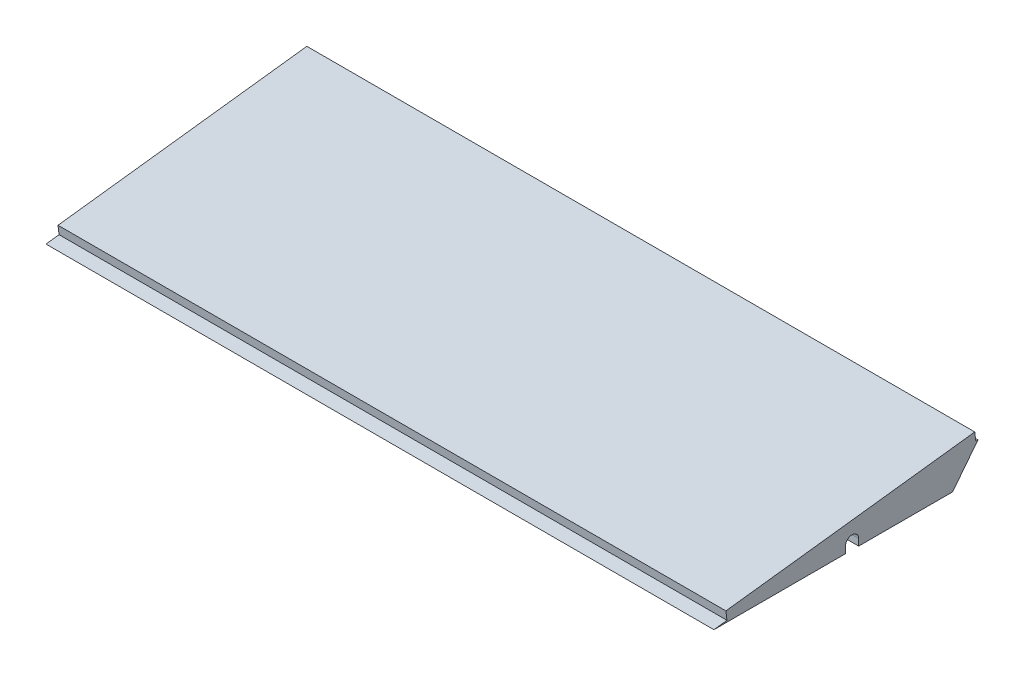
SolidWorks part; units mm, degrees
ref_plane "Front Plane" through (0, 0, 0) normal (0, 0, 1) x (1, 0, 0)
ref_plane "Top Plane" through (0, 0, 0) normal (0, 1, 0) x (1, 0, 0)
ref_plane "Right Plane" through (0, 0, 0) normal (1, 0, 0) x (0, 0, -1)
sketch "Sketch1" plane through (0, 0, 0) normal (1, 0, 0) x (0, 0, -1)
  line L0 (0, 0) -> (34.5629, 4.2438)
  line L2 (0, 0) -> (29.8632, 0)
  dimension "D1" = 7
ref_plane "Plane1" through (0, 0, 0) normal (0, -0.9925, -0.1219) x (0, 0.1219, -0.9925)
sketch "Sketch2" plane through (0, 0, 0) normal (0, -0.9925, -0.1219) x (0, 0.1219, -0.9925)
  line L1 (0, 0) -> (121.3, 0)
  line L2 (0, 0) -> (0, 304.5)
  line L3 (0, 304.5) -> (121.3, 304.5)
  line L4 (121.3, 0) -> (121.3, 304.5)
  dimension "D1" = 304.5
  dimension "D2" = 121.3
extrude "Boss-Extrude1" add sketch "Sketch2" along normal blind 20
sketch "Sketch4" plane through (304.5, 0, 0) normal (1, 0, 0) x (0, 0, -1)
  line L0 (0, 0) -> (5.9553, 0.7312)
  line L1 (-4.5988, -0.5647) -> (4.5988, 0.5647) construction
  line L2 (5.9553, 0.7312) -> (6.4428, -3.239)
  line L3 (6.4428, -3.239) -> (0.4875, -3.9702)
  line L4 (2.4374, -19.8509) -> (0, 0) construction
  line L5 (0.4875, -3.9702) -> (0, 0)
  line L6 (119.4033, 14.6609) -> (119.8908, 10.6907)
  line L7 (120.3958, 14.7828) -> (0, 0) construction
  line L8 (119.8908, 10.6907) -> (120.8833, 10.8126)
  line L9 (122.8332, -5.0682) -> (120.3958, 14.7828) construction
  line L10 (120.8833, 10.8126) -> (120.3958, 14.7828)
  line L11 (120.3958, 14.7828) -> (119.4033, 14.6609)
  line L12 (0.4875, -3.9702) -> (109.3338, -3.9702)
  line L13 (109.3338, -3.9702) -> (120.8833, 10.8126)
  line L14 (0.4875, -3.9702) -> (2.4374, -19.8509)
  line L15 (2.4374, -19.8509) -> (122.8332, -5.0682)
  line L16 (122.8332, -5.0682) -> (120.8833, 10.8126)
  line L17 (0.4875, -3.9702) -> (109.3338, -3.9702)
  line L18 (120.8833, 10.8126) -> (109.3338, -3.9702)
  line L19 (122.8332, -5.0682) -> (120.8833, 10.8126)
  line M8 (120.3958, 14.7828) -> (0, 0)
  line M9 (0, 0) -> (2.4374, -19.8509)
  line M10 (2.4374, -19.8509) -> (122.8332, -5.0682)
  line M11 (122.8332, -5.0682) -> (120.3958, 14.7828)
  dimension "D1" = 6
  dimension "D2" = 4
  dimension "D3" = 114.3
  dimension "D4" = 4
  dimension "D5" = 45
extrude "Cut-Extrude2" cut sketch "Sketch4" against normal through all contours L13 L12 M9 M10 M11 | L3 L2 M8 M9 | L10 L11 L6 L8 region at (304.5, -1.6195, -3.2214) region at (304.5, -8.3968, -50.8691)
sketch "Sketch6" plane through (304.5, 0, 0) normal (1, 0, 0) x (0, 0, -1)
  line L0 (0.4875, -3.9702) -> (109.3338, -3.9702) construction
  line L1 (60.4875, -3.9702) -> (66.4875, -3.9702)
  line L2 (60.4875, -3.9702) -> (60.4875, 2.0298)
  line L3 (60.4875, 2.0298) -> (66.4875, 2.0298)
  line L4 (66.4875, -3.9702) -> (66.4875, 2.0298)
  dimension "D1" = 6
  dimension "D2" = 6
  dimension "D3" = 60
extrude "Cut-Extrude3" cut sketch "Sketch6" against normal blind 155.4
sketch "Sketch8" plane through (0, 0, -66.4875) normal (0, 0, 1) x (1, 0, 0)
  line L0 (149.1, 2.0298) -> (304.5, 2.0298) construction
  line L1 (149.1, -3.9702) -> (155.1, -3.9702)
  line L2 (149.1, -3.9702) -> (149.1, 2.0298)
  line L3 (149.1, 2.0298) -> (155.1, 2.0298)
  line L4 (155.1, -3.9702) -> (155.1, 2.0298)
  dimension "D1" = 6
extrude "Cut-Extrude4" cut sketch "Sketch8" against normal through all
fillet "Fillet2" radius 3 6 edges at (155.1, 2.0298, -90.2545) (149.1, 2.0298, -87.2545) (229.8, 2.0298, -66.4875) (226.8, 2.0298, -60.4875) (155.1, -0.9702, -66.4875) (149.1, -0.9702, -60.4875)
